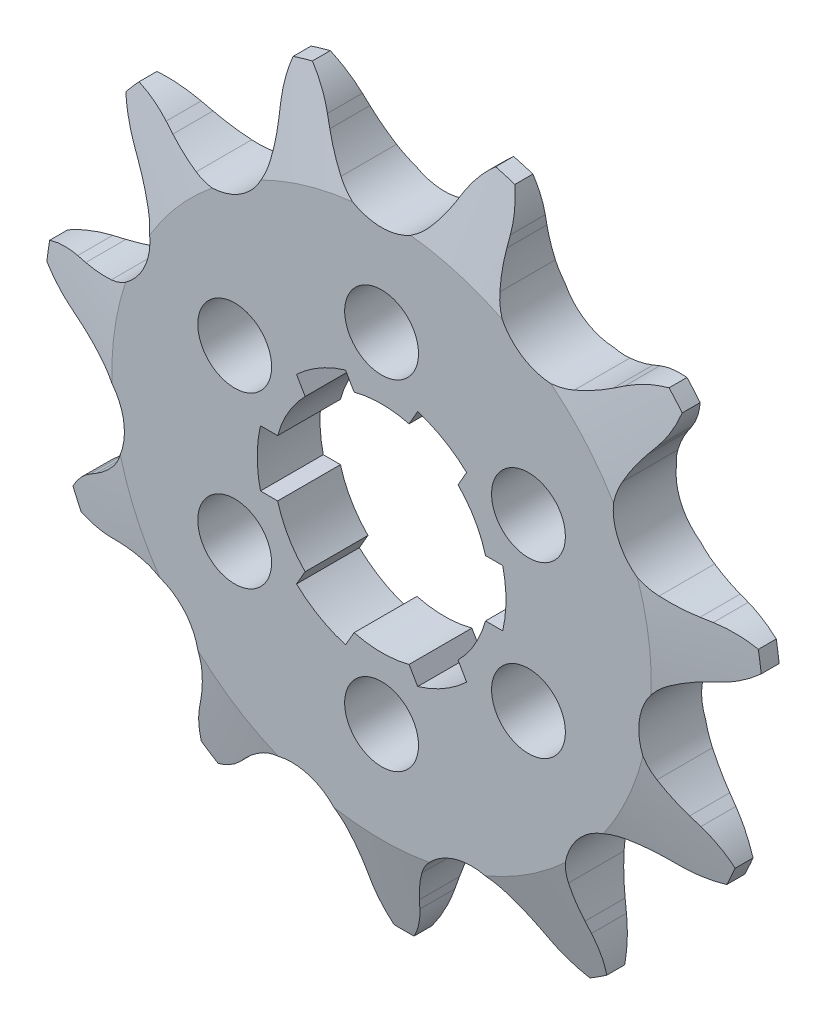
SolidWorks part; units mm, degrees
material "AISI 4130 Steel, annealed at 865C"
ref_plane "Front Plane" through (0, 0, 0) normal (0, 0, 1) x (1, 0, 0)
ref_plane "Top Plane" through (0, 0, 0) normal (0, 1, 0) x (1, 0, 0)
ref_plane "Right Plane" through (0, 0, 0) normal (1, 0, 0) x (0, 0, -1)
sketch "Sketch0" plane through (0, 0, 0) normal (0, 0, 1) x (1, 0, 0)
  line L0 (7.9375, -27.0326) -> (0, 0) construction
  line L1 (0, 0) -> (21.2924, -18.45) construction
  line L2 (0, 0) -> (-7.9375, -27.0326) construction
  line L3 (7.9375, -27.0326) -> (21.2924, -18.45) construction
  line L4 (7.9375, -27.0326) -> (-7.9375, -27.0326) construction
  line L5 (13.7041, -25.3103) -> (13.0504, -24.6313)
  line L6 (7.9375, -27.0326) -> (0, -29.3633) construction
  line L7 (2.1552, -28.7014) -> (2.338, -27.7767)
  line L8 (0, -27.0326) -> (0, -31.7951) construction
  line L9 (10.7525, -22.7279) -> (3.4891, -33.8353) construction
  line L10 (0, 0) -> (0, -27.0326) construction
  line L11 (13.0504, -24.6313) -> (3.4891, -33.8353) construction
  line L12 (0, -31.7951) -> (0, -32.9086) construction
  line L13 (19.9035, -19.3426) -> (13.7041, -25.3103) construction
  circle A0 centre (0, 0) radius 31.7951 construction
  circle A1 centre (0, 0) radius 28.1739 construction
  arc A2 (-8.2356, -35.414) -> (26.0745, -25.3397) centre (0, 0) ccw
  circle A3 centre (0, 0) radius 32.9086 construction
  circle A4 centre (7.9375, -27.0326) radius 5.08 construction
  arc A7 (10.7525, -22.7279) -> (3.242, -24.9331) centre (7.9375, -27.0326) ccw
  circle A8 centre (7.9375, -27.0326) radius 5.1435 construction
  arc A9 (13.7041, -25.3103) -> (26.0745, -25.3397) centre (19.9035, -19.3426) ccw
  arc A10 (13.0504, -24.6313) -> (10.7525, -22.7279) centre (3.4891, -33.8353) ccw
  arc A11 (2.1552, -28.7014) -> (-8.2356, -35.414) centre (-6.2865, -27.0326) cw
  arc A12 (2.338, -27.7767) -> (3.242, -24.9331) centre (15.3575, -30.3504) cw
  dimension "D1" = 5.1435
  dimension "R" = 5.1435
sketch "Sketch1" plane through (0, 0, 0) normal (1, 0, 0) x (0, 0, -1)
  line L0 (2.7781, 0) -> (-2.7781, 0)
  line L1 (-2.7781, 0) -> (-2.7781, 23.8576)
  line L2 (-2.7781, 23.8576) -> (-0.7937, 31.7951)
  line L3 (-0.7937, 31.7951) -> (0.7937, 31.7951)
  line L4 (0.7937, 31.7951) -> (2.7781, 23.8576)
  line L5 (2.7781, 23.8576) -> (2.7781, 0)
  line L7 (0, 31.7951) -> (0, 0) construction
  line L8 (-2.7781, 23.8576) -> (2.7781, 23.8576) construction
  line L9 (0, 31.7951) -> (0, -31.7951) construction
  line L10 (-2.7781, 23.8576) -> (-2.7781, 31.7951) construction
  line L11 (-2.7781, 31.7951) -> (-0.7937, 31.7951) construction
  line L12 (0.7937, 31.7951) -> (2.7781, 31.7951) construction
  line L13 (2.7781, 31.7951) -> (2.7781, 23.8576) construction
revolve "Revolve1" add sketch "Sketch1" angle 360 mid plane about L0
extrude "Cut-Extrude1" cut sketch "Sketch0" against normal through all and the other way through all
pattern_circular "CirPattern1" count 11 over 360 about axis through (0, 0, -2.7781) along (0, 0, -1) of "Cut-Extrude1"
sketch "Sketch2" plane through (0, 0, 0) normal (0, 0, 1) x (1, 0, 0)
  circle A0 centre (0, 0) radius 7.9375 construction
  circle A1 centre (0, 0) radius 30.1625
  circle A2 centre (0, 0) radius 36.957 construction
  dimension "Bore" = 15.875
  dimension "Hub Dia." = 60.325
  dimension "OD" = 73.914
sketch "Sketch3" plane through (0, 0, 0) normal (0, 0, 1) x (1, 0, 0)
  circle A1 centre (0, 0) radius 8.5
  circle A2 centre (0, 0) radius 36.957 construction
  circle A3 centre (0, 0) radius 36.957
  dimension "D1" = 17
extrude "Cut-Extrude2" cut sketch "Sketch3" along normal through all and the other way through all flip side to cut
sketch "Sketch4" plane through (0, 0, -2.7781) normal (0, 0, -1) x (-1, 0, 0)
  line L0 (0, 0) -> (0, 15.875) construction
  circle A0 centre (0, 15.875) radius 3.175
  circle A1 centre (13.7482, 7.9375) radius 3.175
  circle A2 centre (13.7482, -7.9375) radius 3.175
  circle A3 centre (0, -15.875) radius 3.175
  circle A4 centre (-13.7482, -7.9375) radius 3.175
  circle A5 centre (-13.7482, 7.9375) radius 3.175
  point P17 (0, 0)
  dimension "D1" = 6
extrude "Cut-Extrude3" [suppressed] cut sketch "Sketch4" against normal through all
sketch "Sketch5" plane through (0, 0, 2.7781) normal (0, 0, 1) x (1, 0, 0)
  line L0 (0, 0) -> (8.5, 0) construction
  line L1 (8.5, 0) -> (11, 0) construction
  circle A0 centre (0, 0) radius 11 construction
  circle A1 centre (0, 0) radius 8.5 construction
sketch "Sketch6" plane through (0, 0, -2.7781) normal (0, 0, -1) x (-1, 0, 0)
  circle A0 centre (0, 0) radius 28.024 construction
  circle A1 centre (0, 0) radius 24.2521 construction
ref_plane "Plane1" [suppressed] through (-29.6833, 20.4889, 0) normal (-0.823, 0.5681, 0) x (0, 0, 1)
ref_plane "Plane2" [suppressed] through (-35.8049, 4.3475, 0) normal (-0.9927, 0.1205, 0) x (0, 0, 1)
ref_plane "Plane3" [suppressed] through (-33.724, -12.7898, 0) normal (-0.935, -0.3546, 0) x (0, 0, 1)
ref_plane "Plane4" [suppressed] through (-23.9174, -26.9972, 0) normal (-0.6631, -0.7485, 0) x (-0.7485, 0.6631, 0)
ref_plane "Plane5" [suppressed] through (-8.6316, -35.0198, 0) normal (-0.2393, -0.9709, 0) x (-0.9709, 0.2393, 0)
sketch "Sketch7" [suppressed] plane through (-29.6833, 20.4889, 0) normal (-0.823, 0.5681, 0) x (0, 0, 1)
  line L0 (-6.5106, 0) -> (7.7601, 0)
sketch "Sketch8" [suppressed] plane through (-35.8049, 4.3475, 0) normal (-0.9927, 0.1205, 0) x (0, 0, 1)
  line L0 (-7.786, 0) -> (10.2102, 0)
sketch "Sketch9" [suppressed] plane through (-33.724, -12.7898, 0) normal (-0.935, -0.3546, 0) x (0, 0, 1)
  line L0 (-7.6671, 0) -> (14.0341, 0)
  line L1 (-2.7781, 6.1399) -> (2.7781, 6.1399) construction
sketch "Sketch10" [suppressed] plane through (-23.9174, -26.9972, 0) normal (-0.6631, -0.7485, 0) x (-0.7485, 0.6631, 0)
  line L0 (0, -3.5829) -> (0, 5.4944)
sketch "Sketch11" [suppressed] plane through (-8.6316, -35.0198, 0) normal (-0.2393, -0.9709, 0) x (-0.9709, 0.2393, 0)
  line L0 (0, -5.4358) -> (0, 8.5188)
split line "Split Line7" [suppressed]
split line "Split Line8" [suppressed]
split line "Split Line9" [suppressed]
split line "Split Line10" [suppressed]
split line "Split Line11" [suppressed]
ref_plane "Motor Sprocket Middle Plane" through (0, 0, -0.0019) normal (0, 0, 1) x (1, 0, 0)
sketch "Sketch12" plane through (0, 0, -2.7781) normal (0, 0, -1) x (-1, 0, 0)
  line L0 (10.7121, 2.5) -> (8.6458, 2.5)
  line L1 (10.7121, -2.5) -> (8.6458, -2.5)
  line L2 (7.5211, -8.027) -> (6.488, -6.2375)
  line L3 (3.191, -10.527) -> (2.1578, -8.7375)
  line L4 (-3.191, -10.527) -> (-2.1578, -8.7375)
  line L5 (-7.5211, -8.027) -> (-6.488, -6.2375)
  line L6 (-10.7121, -2.5) -> (-8.6458, -2.5)
  line L7 (-10.7121, 2.5) -> (-8.6458, 2.5)
  line L8 (-7.5211, 8.027) -> (-6.488, 6.2375)
  line L9 (-3.191, 10.527) -> (-2.1578, 8.7375)
  line L10 (3.191, 10.527) -> (2.1578, 8.7375)
  line L11 (7.5211, 8.027) -> (6.488, 6.2375)
  arc A0 (2.1578, 8.7375) -> (-2.1578, 8.7375) centre (0, 0) ccw
  arc A1 (-3.191, 10.527) -> (-7.5211, 8.027) centre (0, 0) ccw
  arc A2 (-6.488, 6.2375) -> (-8.6458, 2.5) centre (0, 0) ccw
  arc A3 (-10.7121, 2.5) -> (-10.7121, -2.5) centre (0, 0) ccw
  arc A4 (-8.6458, -2.5) -> (-6.488, -6.2375) centre (0, 0) ccw
  arc A5 (-7.5211, -8.027) -> (-3.191, -10.527) centre (0, 0) ccw
  arc A6 (-2.1578, -8.7375) -> (2.1578, -8.7375) centre (0, 0) ccw
  arc A7 (3.191, -10.527) -> (7.5211, -8.027) centre (0, 0) ccw
  arc A8 (6.488, -6.2375) -> (8.6458, -2.5) centre (0, 0) ccw
  arc A9 (10.7121, -2.5) -> (10.7121, 2.5) centre (0, 0) ccw
  arc A10 (8.6458, 2.5) -> (6.488, 6.2375) centre (0, 0) ccw
  arc A11 (7.5211, 8.027) -> (3.191, 10.527) centre (0, 0) ccw
  point P9 (4.5255, -11.1498)
  point P10 (0, 0)
  point P30 (0, 0)
  dimension "D1" = 18
  dimension "D2" = 22
  dimension "D3" = 5
  dimension "D4" = 6
extrude "Cut-Extrude4" cut sketch "Sketch12" against normal through all
sketch "Sketch14" plane through (0, 0, 2.7781) normal (0, 0, 1) x (1, 0, 0)
  circle A0 centre (-12.9904, -7.5) radius 2.6
  circle A1 centre (0, 15) radius 2.6
  circle A2 centre (12.9904, -7.5) radius 2.6
  circle A3 centre (-12.9904, -7.5) radius 3
  circle A4 centre (0, 15) radius 3
  circle A5 centre (12.9904, -7.5) radius 3
  point P8 (0, 0)
  point P9 (-7.9266, 12.7346)
  point P12 (0, 0)
  dimension "D1" = 5.2
  dimension "D4" = 20.7808
  dimension "D5" = 6
  dimension "D3" = 15
  dimension "D2" = 3
sketch "Sketch13" plane through (0, 0, -0.0019) normal (0, 0, 1) x (1, 0, 0)
  circle A0 centre (0, 0) radius 28.1739 construction
  circle A1 centre (0, 0) radius 20.6739
  circle A2 centre (0, 15) radius 4.7625
  circle A3 centre (0, 0) radius 11
  circle A4 centre (0, 0) radius 15 construction
  point P14 (-0.562, 15)
  point P15 (-0.6807, 15)
  dimension "D1" = 7.5
  dimension "D2" = 9.525
sketch "Sketch15" plane through (0, 0, 2.7781) normal (0, 0, 1) x (1, 0, 0)
  circle A0 centre (0, 15) radius 3.2639
  circle A1 centre (12.9904, 7.5) radius 3.2639
  circle A2 centre (12.9904, -7.5) radius 3.2639
  circle A3 centre (0, -15) radius 3.2639
  circle A4 centre (-12.9904, -7.5) radius 3.2639
  circle A5 centre (-12.9904, 7.5) radius 3.2639
  point P3 (15.2662, 8.7433)
  point P4 (0, 0)
  point P15 (0, 0)
  dimension "D1" = 6.5278
  dimension "D2" = 6
extrude "Cut-Extrude5" cut sketch "Sketch15" against normal through all
sketch "Sketch16" plane through (0, 0, -0.0019) normal (0, 0, 1) x (1, 0, 0)
  circle A0 centre (0, 0) radius 9.525
  dimension "D1" = 19.05
extrude "Cut-Extrude6" cut sketch "Sketch16" against normal through all both and the other way through all
equation "\"360/N@Sketch0\" = 360/\"Teeth@CirPattern1\""
equation "\"Ds@Sketch0\" = 1.005 * \"Dr@Sketch0\" + 0.003"
equation "\"R@Sketch0\" = 1/2 * \"Ds@Sketch0\""
equation "\"A@Sketch0\" = 35 +  ( 60 / \"Teeth@CirPattern1\" ) "
equation "\"B@Sketch0\" = 18 -  ( 56 / \"Teeth@CirPattern1\" )"
equation "\"ac@Sketch0\" = 0.8 * \"Dr@Sketch0\""
equation "\"ab@Sketch0\" = 1.4 * \"Dr@Sketch0\""
equation "\"J@Sketch0\" = 0.3 * \"Pitch@Sketch0\""
equation "\"h@Sketch1\" = \"Pitch@Sketch0\" / 2"
equation "\"g@Sketch1\" = \"h@Sketch1\" / 4"
